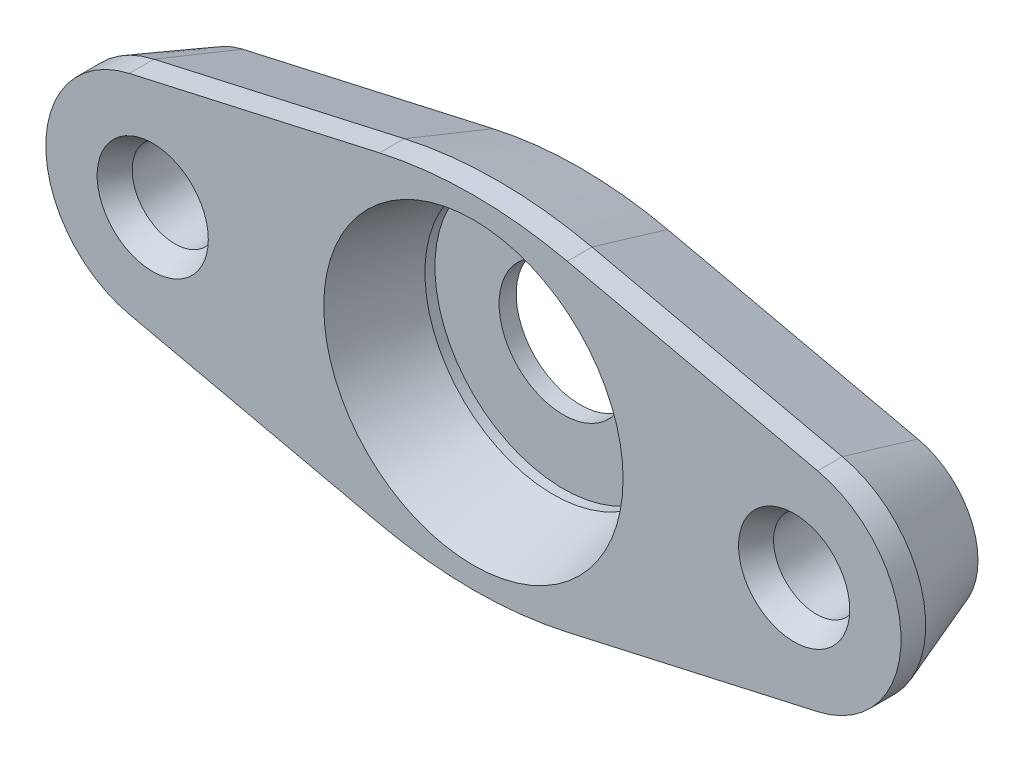
SolidWorks part; units mm, degrees
ref_plane "Front Plane" through (0, 0, 0) normal (0, 0, 1) x (1, 0, 0)
ref_plane "Top Plane" through (0, 0, 0) normal (0, 1, 0) x (1, 0, 0)
ref_plane "Right Plane" through (0, 0, 0) normal (1, 0, 0) x (0, 0, -1)
sketch "Sketch1" plane through (0, 0, 0) normal (0, 0, 1) x (1, 0, 0)
  line L0 (-8.0488, 2.439) -> (-2.1951, 3.7561)
  line L1 (2.1951, 3.7561) -> (8.0488, 2.439)
  line L2 (-8.0488, -2.439) -> (-2.1951, -3.7561)
  line L3 (2.1951, -3.7561) -> (8.0488, -2.439)
  line L4 (0, 9.0509) -> (0, -9.0509) construction
  line L5 (-11.5511, 0) -> (12.1784, 0) construction
  circle A0 centre (0, 0) radius 3 construction
  circle A1 centre (7.5, 0) radius 1
  circle A2 centre (-7.5, 0) radius 1
  arc A3 (-8.0488, 2.439) -> (-8.0488, -2.439) centre (-7.5, 0) ccw
  arc A4 (8.0488, -2.439) -> (8.0488, 2.439) centre (7.5, 0) ccw
  arc A5 (-2.1951, -3.7561) -> (2.1951, -3.7561) centre (0, 6) ccw
  arc A6 (-2.1951, 3.7561) -> (2.1951, 3.7561) centre (0, -6) cw
  point P17 (0, -4.25)
  point P22 (0, 4.25)
  dimension "D1" = 2
  dimension "D2" = 15
  dimension "D3" = 5
  dimension "D4" = 6
  dimension "D5" = 10
  dimension "D6" = 6
extrude "Boss-Extrude1" add sketch "Sketch1" along normal blind 2.5
sketch "Sketch2" plane through (0, 0, 2.5) normal (0, 0, 1) x (1, 0, 0)
  circle A0 centre (0, 0) radius 3
  dimension "D1" = 6
extrude "Cut-Extrude1" cut sketch "Sketch2" against normal blind 2.1
chamfer "Chamfer1" distance 0.7 angle 70 8 edges at (-5.122, 3.0976, 0) (-10, 0, 0) (0, 4, 0) (-5.122, -3.0976, 0) (5.122, 3.0976, 0) (0, -4, 0) (10, 0, 0) (5.122, -3.0976, 0) first distance on face at (0, 0, 0)
chamfer "Chamfer2" distance 0.5 angle 75 1 edges at (3, 0, 2.5) first distance on face at (3, 0, 2.5)
chamfer "Chamfer3" distance 0.3 angle 60 2 edges at (8.5, 0, 2.5) (-6.5, 0, 2.5) first distance on face at (3.5, 0, 2.5)
sketch "Sketch3" plane through (0, 0, 0.4) normal (0, 0, 1) x (1, 0, 0)
  circle A0 centre (0, 0) radius 1.5
  dimension "D1" = 3
extrude "Cut-Extrude2" cut sketch "Sketch3" against normal blind 10
